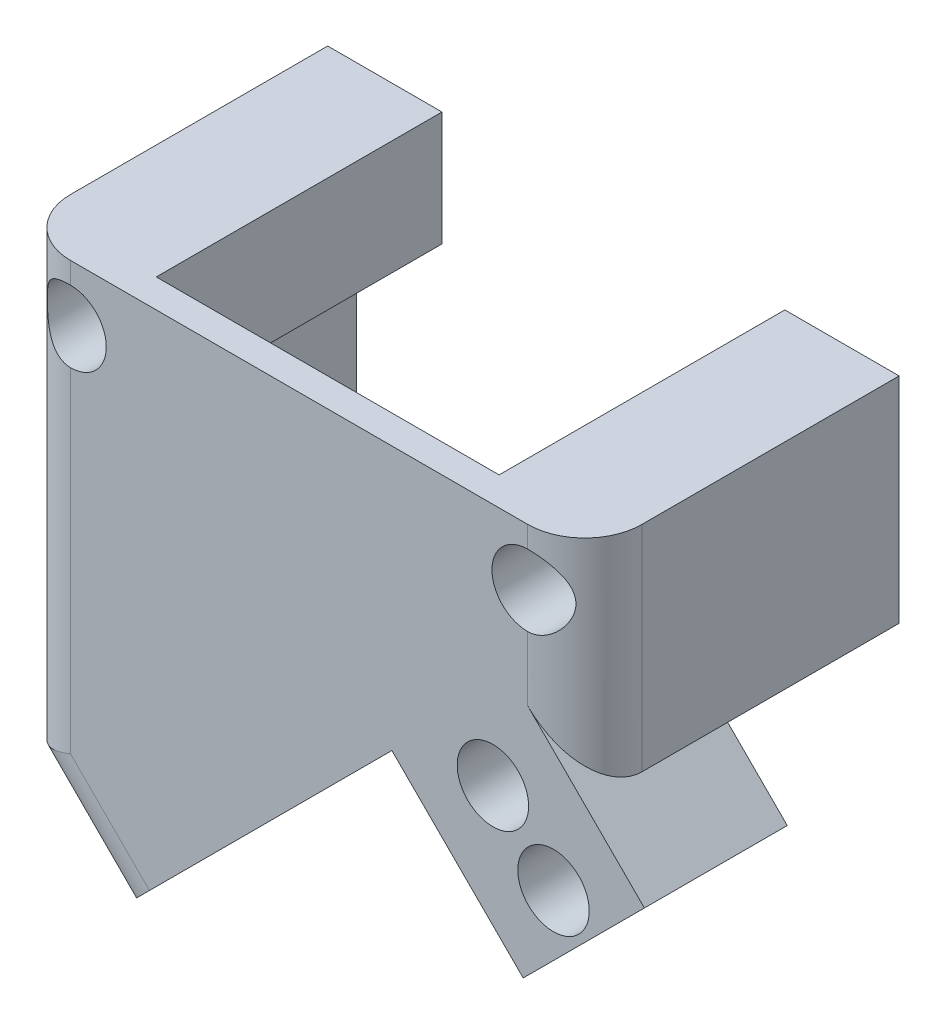
SolidWorks part; units mm, degrees
ref_plane "Front" through (0, 0, 0) normal (0, 0, 1) x (1, 0, 0)
ref_plane "Top" through (0, 0, 0) normal (0, 1, 0) x (1, 0, 0)
ref_plane "Right" through (0, 0, 0) normal (1, 0, 0) x (0, 0, -1)
sketch "Sketch2" plane through (0, 0, 0) normal (0, 0, 1) x (1, 0, 0)
  line L0 (-6.3781, -22.9122) -> (3.5214, -13.0127)
  line L1 (3.5214, -13.0127) -> (8.1176, -17.6089)
  line L2 (8.1176, -17.6089) -> (12.3603, -13.3663)
  line L3 (12.3603, -13.3663) -> (10.2745, -11.2805)
  line L4 (10.2745, -11.2805) -> (10.2745, -3.7805)
  line L5 (10.2745, -3.7805) -> (-9.7255, -3.7805)
  line L6 (-9.7255, -3.7805) -> (-9.7255, -19.5648)
  line L7 (-9.7255, -19.5648) -> (-6.3781, -22.9122)
  line L8 (-5.7255, -7.7805) -> (-5.7255, -4.7805)
  line L9 (-5.7255, -4.7805) -> (6.2745, -4.7805)
  line L10 (-5.7255, -7.7805) -> (-8.7255, -7.7805)
  line L13 (6.2745, -8.8454) -> (6.2745, -4.7805)
  line L14 (-6.3781, -21.498) -> (6.2745, -8.8454)
  line L16 (-8.7255, -7.7805) -> (-8.7255, -19.1506)
  line L17 (-8.7255, -19.1506) -> (-6.3781, -21.498)
extrude "Boss-Extrude1" add sketch "Sketch2" along normal blind 11
sketch "Sketch3" plane through (0, 0, 0) normal (0, 0, 1) x (1, 0, 0)
  line L0 (-6.3781, -22.9122) -> (3.5214, -13.0127)
  line L1 (3.5214, -13.0127) -> (8.1176, -17.6089)
  line L2 (8.1176, -17.6089) -> (12.3603, -13.3663)
  line L3 (12.3603, -13.3663) -> (10.2745, -11.2805)
  line L4 (10.2745, -11.2805) -> (10.2745, -3.7805)
  line L5 (10.2745, -3.7805) -> (-9.7255, -3.7805)
  line L6 (-9.7255, -3.7805) -> (-9.7255, -19.5648)
  line L7 (-9.7255, -19.5648) -> (-6.3781, -22.9122)
extrude "Boss-Extrude2" add sketch "Sketch3" against normal blind 1 from offset 11
sketch "Sketch6" plane through (0, 0, 0) normal (0, 0, 1) x (1, 0, 0)
  line L0 (-5.7255, -3.7805) -> (-5.7255, -4.7805)
  line L2 (-5.7255, -3.7805) -> (6.2745, -3.7805)
  line L3 (-5.7255, -4.7805) -> (6.2745, -4.7805)
  line L4 (6.2745, -4.7805) -> (6.2745, -3.7805)
extrude "Upper Tube Opening" cut sketch "Sketch6" along normal blind 10
sketch "Sketch7" plane through (8.2671, -8.2671, 0) normal (0.7071, -0.7071, 0) x (0, 0, -1)
  line L0 (-8, -19.7114) -> (0, -19.7114)
  line L2 (0, -19.7114) -> (0, -6.7114)
  line L3 (0, -6.7114) -> (-10, -6.7114)
  line L5 (-10, -6.7114) -> (-10, -17.7114)
  arc A0 (-8, -19.7114) -> (-10, -17.7114) centre (-8, -17.7114) cw
extrude "Lower Tube Opening" cut sketch "Sketch7" against normal blind 1
sketch "Sketch4" plane through (0, 0, 0) normal (0, 0, 1) x (1, 0, 0)
  line L0 (0.2745, -5.7805) -> (8.2745, -5.7805) construction
  line L1 (10.2389, -15.4876) -> (9.1783, -14.4269) construction
  line L2 (9.1783, -14.4269) -> (7.057, -12.3056) construction
  line L3 (-7.7255, -5.7805) -> (0.2745, -5.7805) construction
  line L4 (0.2745, -5.7805) -> (0.2745, -3.7805) construction
  circle A0 centre (9.1783, -14.4269) radius 0.8
  circle A1 centre (7.057, -12.3056) radius 0.8
  circle A2 centre (-7.7255, -5.7805) radius 0.8
  circle A3 centre (8.2745, -5.7805) radius 0.8
extrude "Screw Holes" cut sketch "Sketch4" along normal through all
sketch "Sketch5" plane through (0, 0, 0) normal (0, 0, 1) x (1, 0, 0)
  circle A0 centre (-7.7255, -5.7805) radius 1.25
  circle A1 centre (8.2745, -5.7805) radius 1.25
  circle A2 centre (7.057, -12.3056) radius 1.25
  circle A3 centre (9.1783, -14.4269) radius 1.25
extrude "Screw Heads" cut sketch "Sketch5" against normal blind 3 from offset 11
fillet "Fillet1" radius 2 3 edges at (-8.0518, -21.2385, 11) (10.2745, -7.5305, 11) (-9.7255, -11.6727, 11)
sketch "Sketch10" plane through (0, 0, 0) normal (0, 0, 1) x (1, 0, 0)
  line L0 (12.3603, -13.3663) -> (8.1176, -17.6089)
  line L1 (8.1176, -17.6089) -> (2.8143, -12.3056)
  line L2 (12.3603, -13.3663) -> (7.057, -8.063)
  line L3 (7.057, -8.063) -> (2.8143, -12.3056)
extrude "Cut-Extrude1" cut sketch "Sketch10" along normal blind 6
